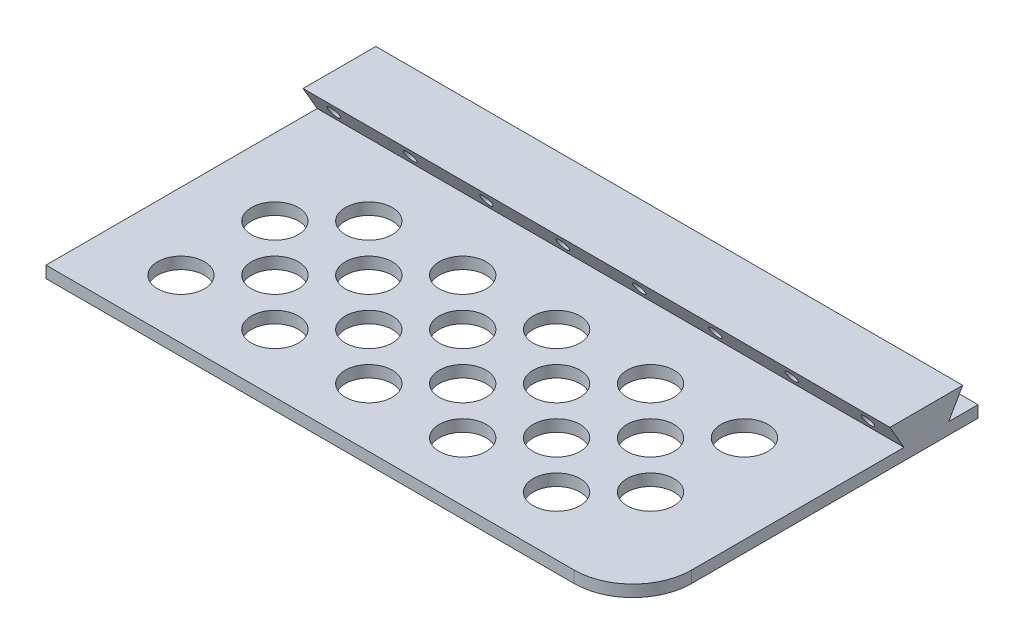
SolidWorks part; units mm, degrees
ref_plane "Front Plane" through (0, 0, 0) normal (0, 0, 1) x (1, 0, 0)
ref_plane "Top Plane" through (0, 0, 0) normal (0, 1, 0) x (1, 0, 0)
ref_plane "Right Plane" through (0, 0, 0) normal (1, 0, 0) x (0, 0, -1)
sketch "Sketch1" plane through (0, 0, 0) normal (0, 1, 0) x (1, 0, 0)
  line L1 (50, -50) -> (-50, -50)
  line L2 (50, -50) -> (50, 50)
  line L3 (50, 50) -> (-50, 50)
  line L4 (-50, -50) -> (-50, 50)
  line L5 (50, -50) -> (-50, 50) construction
  line L6 (50, 50) -> (-50, -50) construction
  point P0 (0, 0)
  dimension "D1" = 100
  dimension "D2" = 100
extrude "Boss-Extrude1" add sketch "Sketch1" along normal blind 2
sketch "Sketch2" plane through (50, 0, 0) normal (1, 0, 0) x (0, 0, -1)
  line L0 (-3.8, 2) -> (-6.2018, 6.16)
  line L1 (-50, 2) -> (50, 2) construction
  line L2 (-6.2018, 6.16) -> (6.2018, 6.16)
  line L3 (6.2018, 6.16) -> (3.8, 2)
  line L4 (3.8, 2) -> (-3.8, 2)
  line L5 (0, -1000) -> (0, 49000) construction
  dimension "D1" = 60
  dimension "D2" = 4.16
  dimension "D3" = 60
  dimension "D4" = 7.6
extrude "Boss-Extrude2" add sketch "Sketch2" against normal up to surface (100 mm away) up to face at (-50, 1, 0)
ref_point "Point1"
ref_axis "Axis1" through (0, 0, 0) along (0, 1, 0)
ref_point "Point2"
ref_axis "Axis2" through (-50, 1.5591, 0) along (1, 0, 0)
ref_point "CM"
fillet "Fillet1" radius 10 2 edges at (50, 1, -50) (50, 1, 50)
sketch "Sketch3" plane through (0, 2, 0) normal (0, 1, 0) x (1, 0, 0)
  line L1 (-1000, 0) -> (49000, 0) construction
  circle A1 centre (35, -16) radius 4
  circle A2 centre (27, -24) radius 4
  dimension "D1" = 8
  dimension "D2" = 35
  dimension "D5" = 8
  dimension "D3" = 16
  dimension "D4" = 8
extrude "Cut-Extrude1" cut sketch "Sketch3" against normal through all
pattern_linear "LPattern1" count 5 spacing 16 along (-1, 0, 0) count 2 spacing 16 along (0, 0, 1) of "Cut-Extrude1"
mirror "Mirror1" about plane through (0, 0, 0) normal (0, 0, 1) of "LPattern1"
sketch "Sketch4" plane through (-50, 0, 0) normal (-1, 0, 0) x (0, 0, 1)
  line L1 (-50, 0) -> (-8.8, 0)
  line L2 (-50, 0) -> (-50, 2)
  line L3 (-50, 2) -> (-8.8, 2)
  line L4 (-8.8, 0) -> (-8.8, 2)
  dimension "D1" = 5
extrude "Cut-Extrude2" cut sketch "Sketch4" against normal through all
sketch "Sketch5" plane through (0, 0, 50) normal (0, 0, 1) x (1, 0, 0)
  line L0 (-50, 2) -> (40, 2) construction
  line L1 (-50, 2) -> (-50, 0) construction
  circle A0 centre (-46, 4) radius 1
  point P6 (0, 0)
  dimension "D2" = 2
  dimension "D4" = 4
  dimension "D1" = 2
extrude "Cut-Extrude3" cut sketch "Sketch5" against normal through all
pattern_linear "LPattern2" count 8 spacing 13 along (1, 0, 0) of "Cut-Extrude3"
